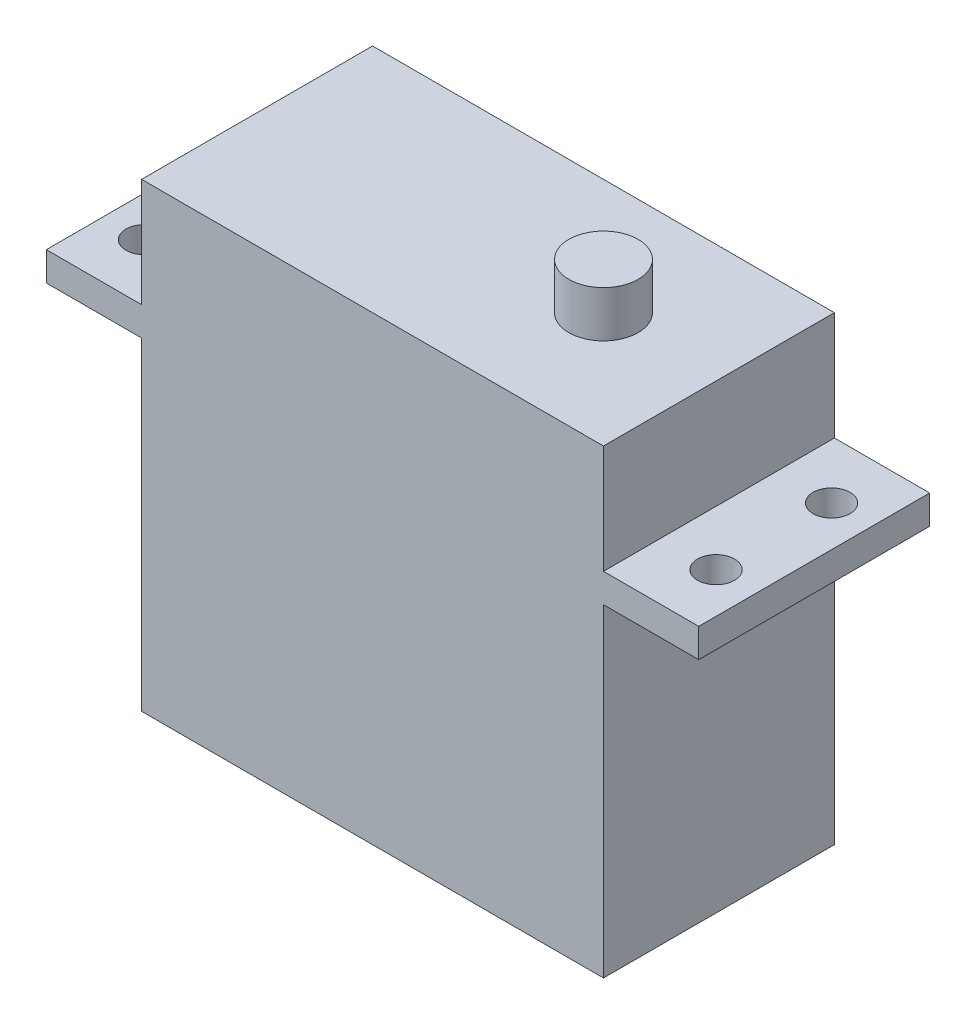
SolidWorks part; units mm, degrees
ref_plane "Front Plane" through (0, 0, 0) normal (0, 0, 1) x (1, 0, 0)
ref_plane "Top Plane" through (0, 0, 0) normal (0, 1, 0) x (1, 0, 0)
ref_plane "Right Plane" through (0, 0, 0) normal (1, 0, 0) x (0, 0, -1)
ref_plane "Case Side" through (0, 0, 14) normal (0, 0, 1) x (1, 0, 0)
sketch "Case Sketch" plane through (0, 0, 14) normal (0, 0, 1) x (1, 0, 0)
  line L0 (-30, 17.6) -> (10, 17.6)
  line L1 (10, 17.6) -> (10, 57.5)
  line L2 (10, 57.5) -> (-30, 57.5)
  line L3 (-30, 57.5) -> (-30, 17.6)
extrude "Case" add sketch "Case Sketch" along normal blind 20
ref_axis "Engine Axis" through (21.075, 0, 0) along (-1, 0, 0)
sketch "Tabs Sketch" plane through (0, 0, 14) normal (0, 0, 1) x (1, 0, 0)
  line L0 (-38.25, 45.6) -> (-30, 45.6)
  line L1 (-30, 45.6) -> (-30, 48.1)
  line L2 (-30, 48.1) -> (-38.25, 48.1)
  line L3 (-38.25, 48.1) -> (-38.25, 45.6)
  line L4 (10, 45.6) -> (18.25, 45.6)
  line L5 (18.25, 45.6) -> (18.25, 48.1)
  line L6 (18.25, 48.1) -> (10, 48.1)
  line L7 (10, 48.1) -> (10, 45.6)
extrude "Tabs" add sketch "Tabs Sketch" along normal blind 20
ref_plane "Shaft Plane" through (0, 0, 24) normal (0, 0, 1) x (1, 0, 0)
sketch "Shaft Sketch" plane through (0, 0, 24) normal (0, 0, 1) x (1, 0, 0)
  line L0 (0, -100) -> (0, 200) construction
  line L1 (0, 57.5) -> (3, 57.5)
  line L2 (3, 57.5) -> (3, 61.5)
  line L3 (3, 61.5) -> (0, 61.5)
  line L4 (0, 61.5) -> (0, 57.5)
revolve "Shaft" add sketch "Shaft Sketch" angle 360 about L0
sketch "Tab Holes Sketch" plane through (0, 0, 0) normal (0, 1, 0) x (1, 0, 0)
  circle A0 centre (-34.75, -19) radius 1.6
  circle A1 centre (-34.75, -29) radius 1.6
  circle A2 centre (14.75, -19) radius 1.6
  circle A3 centre (14.75, -29) radius 1.6
extrude "Tab Holes" cut sketch "Tab Holes Sketch" against normal mid plane 106.2
